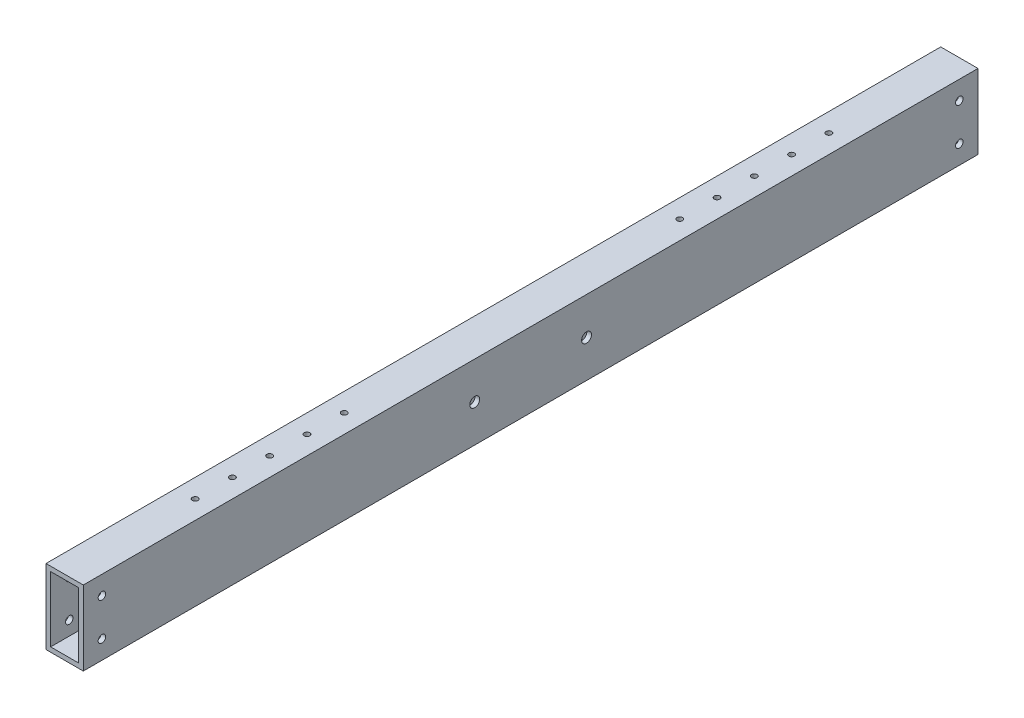
SolidWorks part; units mm, degrees
material "6061-T6 (SS)"
ref_plane "Front Plane" through (0, 0, 0) normal (0, 0, 1) x (1, 0, 0)
ref_plane "Top Plane" through (0, 0, 0) normal (0, 1, 0) x (1, 0, 0)
ref_plane "Right Plane" through (0, 0, 0) normal (1, 0, 0) x (0, 0, -1)
sketch "Sketch1" plane through (0, 0, 0) normal (0, 0, 1) x (1, 0, 0)
  line L0 (-9.525, 22.225) -> (9.525, 22.225)
  line L1 (-12.7, 25.4) -> (12.7, 25.4)
  line L2 (-12.7, 25.4) -> (-12.7, -25.4)
  line L3 (-12.7, -25.4) -> (12.7, -25.4)
  line L4 (12.7, 25.4) -> (12.7, -25.4)
  line L5 (-12.7, 25.4) -> (12.7, -25.4) construction
  line L6 (-12.7, -25.4) -> (12.7, 25.4) construction
  line L7 (9.525, 22.225) -> (9.525, -22.225)
  line L8 (-9.525, -22.225) -> (9.525, -22.225)
  line L9 (-9.525, 22.225) -> (-9.525, -22.225)
  point P0 (0, 0)
  dimension "D1" = 50.8
  dimension "D2" = 25.4
  dimension "D3" = 3.175
extrude "Boss-Extrude1" add sketch "Sketch1" along normal mid plane 609.6
hole_wizard "#10 Clearance Hole1" positions "Sketch4" profile "Sketch3" hole size "#10" standard "ANSI Inch" end condition through all
sketch "Sketch4" plane through (12.7, 0, 0) normal (1, 0, 0) x (0, 0, -1)
  line L0 (-304.8, 25.4) -> (304.8, 25.4) construction
  point P0 (-292.1, 12.7)
  point P13 (-292.1, -12.7)
  dimension "D2" = 12.7
  dimension "D1" = 2
sketch "Sketch3" plane through (12.7, 12.7, 292.1) normal (0, 1, 0) x (0, 0, -1)
  line L0 (0, 0) -> (0, 25.4)
  line L1 (0, 25.4) -> (2.5527, 25.4)
  line L2 (2.5527, 25.4) -> (2.5527, 0)
  line L5 (2.5527, 0) -> (0, 0)
  line L11 (0, -6.35) -> (0, 107.95) construction
  dimension "Thru Hole Dia." = 5.1054
  dimension "Thru Hole Depth" = 25.4
mirror "Mirror1" about plane through (0, 0, 0) normal (0, 0, 1) of "#10 Clearance Hole1"
hole_wizard "1/4 Clearance Hole2" positions "Sketch6" profile "Sketch5" hole size "1/4" standard "ANSI Inch" end condition through all
sketch "Sketch6" plane through (12.7, 0, 0) normal (1, 0, 0) x (0, 0, -1)
  line L0 (-38.1, 0) -> (38.1, 0) construction
  point P0 (-38.1, 0)
  point P2 (38.1, 0)
  dimension "D1" = 76.2
sketch "Sketch5" plane through (12.7, 0, 38.1) normal (0, 1, 0) x (0, 0, -1)
  line L0 (0, 0) -> (0, 25.4)
  line L1 (0, 25.4) -> (3.3782, 25.4)
  line L2 (3.3782, 25.4) -> (3.3782, 0)
  line L5 (3.3782, 0) -> (0, 0)
  line L11 (0, -6.35) -> (0, 107.95) construction
  dimension "Thru Hole Dia." = 6.7564
  dimension "Thru Hole Depth" = 25.4
sketch "Sketch7" plane through (0, 25.4, 0) normal (0, 1, 0) x (1, 0, 0)
  line L0 (-12.7, -304.8) -> (-12.7, 304.8) construction
  line L1 (12.7, 304.8) -> (-12.7, 304.8) construction
  circle A0 centre (0, 215.9) radius 1.905
  circle A1 centre (0, 190.5) radius 1.905
  circle A2 centre (0, 165.1) radius 1.905
  circle A3 centre (0, 139.7) radius 1.905
  circle A4 centre (0, 114.3) radius 1.905
  dimension "D1" = 3.81
  dimension "D2" = 12.7
  dimension "D3" = 88.9
  dimension "D4" = 5
extrude "Cut-Extrude1" cut sketch "Sketch7" against normal through all
mirror "Mirror2" about plane through (0, 0, 0) normal (0, 0, 1) of "Cut-Extrude1"
